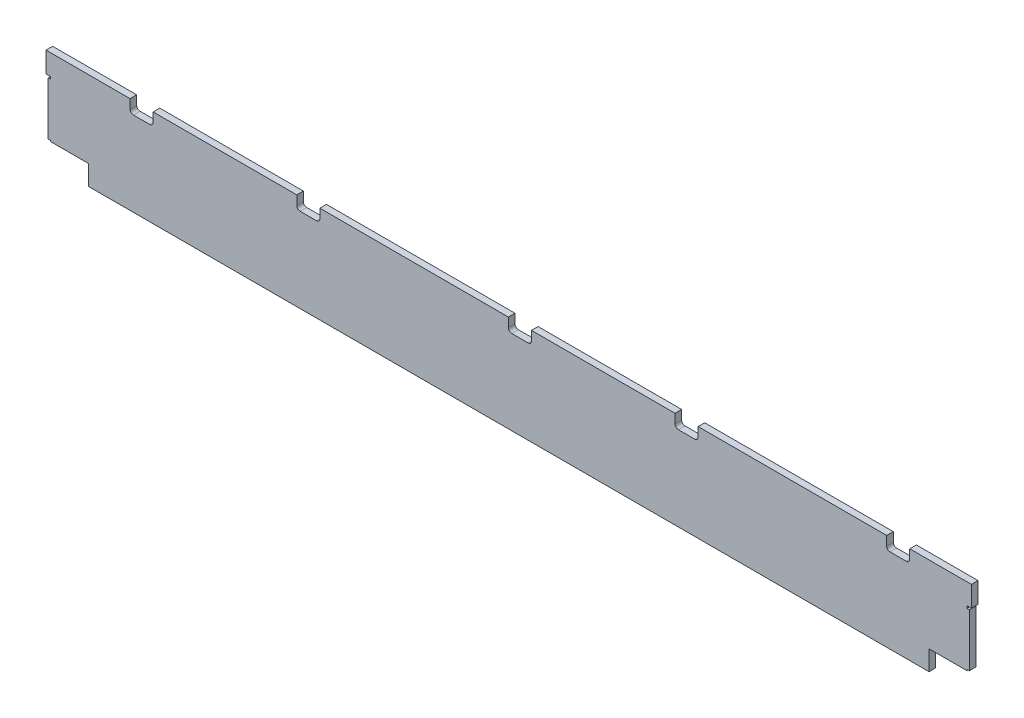
SolidWorks part; units mm, degrees
material "PP Film"
ref_plane "X-Y Datum" through (0, 0, 0) normal (0, 0, 1) x (1, 0, 0)
ref_plane "X-Z Datum" through (0, 0, 0) normal (0, 1, 0) x (1, 0, 0)
ref_plane "Y-Z Datum" through (0, 0, 0) normal (1, 0, 0) x (0, 0, -1)
sketch "Sketch2" plane through (0, 0, 0) normal (0, 0, 1) x (1, 0, 0)
  line L20 (249.4468, -203.714) -> (249.4468, -194.181)
  line L21 (249.4468, -194.181) -> (267.6238, -194.181)
  line L22 (267.6238, -194.181) -> (267.6238, -193.665)
  line L23 (267.6238, -193.665) -> (268.7668, -193.665)
  line L24 (268.7668, -193.665) -> (268.7668, -168.265)
  line L25 (268.7668, -168.265) -> (267.6238, -168.265)
  line L26 (267.6238, -168.265) -> (267.6238, -167.122)
  line L27 (267.6238, -167.122) -> (269.7668, -167.122)
  line L28 (269.7668, -167.122) -> (269.7668, -157.216)
  line L29 (269.7668, -157.216) -> (240.1722, -157.216)
  line L30 (-174.4992, -157.216) -> (-174.4992, -167.122)
  line L31 (-174.4992, -167.122) -> (-172.3562, -167.122)
  line L32 (-172.3562, -167.122) -> (-172.3562, -168.265)
  line L33 (-172.3562, -168.265) -> (-173.4992, -168.265)
  line L34 (-173.4992, -168.265) -> (-173.4992, -193.665)
  line L35 (-173.4992, -193.665) -> (-172.3562, -193.665)
  line L36 (-172.3562, -193.665) -> (-172.3562, -194.181)
  line L37 (-172.3562, -194.181) -> (-154.1792, -194.181)
  line L38 (-154.1792, -194.181) -> (-154.1792, -203.714)
  line L39 (-154.1792, -203.714) -> (249.4468, -203.714)
  line L40 (249.4468, -203.714) -> (249.4468, -194.181)
  line L41 (249.4468, -194.181) -> (267.6238, -194.181)
  line L42 (267.6238, -194.181) -> (267.6238, -193.665)
  line L43 (267.6238, -193.665) -> (268.7668, -193.665)
  line L44 (268.7668, -193.665) -> (268.7668, -168.265)
  line L45 (268.7668, -168.265) -> (267.6238, -168.265)
  line L46 (267.6238, -168.265) -> (267.6238, -167.122)
  line L47 (267.6238, -167.122) -> (269.7668, -167.122)
  line L48 (269.7668, -167.122) -> (269.7668, -157.216)
  line L49 (269.7668, -157.216) -> (240.1722, -157.216)
  line L50 (-174.4992, -157.216) -> (-174.4992, -167.122)
  line L51 (-174.4992, -167.122) -> (-172.3562, -167.122)
  line L52 (-172.3562, -167.122) -> (-172.3562, -168.265)
  line L53 (-172.3562, -168.265) -> (-173.4992, -168.265)
  line L54 (-173.4992, -168.265) -> (-173.4992, -193.665)
  line L55 (-173.4992, -193.665) -> (-172.3562, -193.665)
  line L56 (-172.3562, -193.665) -> (-172.3562, -194.181)
  line L57 (-172.3562, -194.181) -> (-154.1792, -194.181)
  line L58 (-154.1792, -194.181) -> (-154.1792, -203.714)
  line L59 (-154.1792, -203.714) -> (249.4468, -203.714)
  line L120 (-124.6433, -163.248) -> (-132.5323, -163.248)
  line L121 (-124.6433, -163.248) -> (-132.5323, -163.248)
  line L122 (-134.1198, -161.6605) -> (-134.1198, -157.216)
  line L123 (-134.1198, -161.6605) -> (-134.1198, -157.216)
  line L124 (-134.1198, -157.216) -> (-174.4992, -157.216)
  line L125 (-134.1198, -157.216) -> (-174.4992, -157.216)
  line L126 (240.1722, -157.216) -> (240.1722, -161.6605)
  line L127 (240.1722, -157.216) -> (240.1722, -161.6605)
  line L128 (238.5847, -163.248) -> (230.6957, -163.248)
  line L129 (238.5847, -163.248) -> (230.6957, -163.248)
  line L130 (229.1082, -161.6605) -> (229.1082, -157.216)
  line L131 (229.1082, -161.6605) -> (229.1082, -157.216)
  line L132 (229.1082, -157.216) -> (138.5734, -157.216)
  line L133 (229.1082, -157.216) -> (138.5734, -157.216)
  line L134 (138.5734, -157.216) -> (138.5734, -161.6605)
  line L135 (138.5734, -157.216) -> (138.5734, -161.6605)
  line L136 (136.9859, -163.248) -> (129.0969, -163.248)
  line L137 (136.9859, -163.248) -> (129.0969, -163.248)
  line L138 (127.5094, -161.6605) -> (127.5094, -157.216)
  line L139 (127.5094, -161.6605) -> (127.5094, -157.216)
  line L140 (127.5094, -157.216) -> (58.5582, -157.216)
  line L141 (127.5094, -157.216) -> (58.5582, -157.216)
  line L142 (58.5582, -157.216) -> (58.5582, -161.6605)
  line L143 (58.5582, -157.216) -> (58.5582, -161.6605)
  line L144 (56.9707, -163.248) -> (49.0817, -163.248)
  line L145 (56.9707, -163.248) -> (49.0817, -163.248)
  line L146 (47.4942, -161.6605) -> (47.4942, -157.216)
  line L147 (47.4942, -161.6605) -> (47.4942, -157.216)
  line L148 (47.4942, -157.216) -> (-43.0406, -157.216)
  line L149 (47.4942, -157.216) -> (-43.0406, -157.216)
  line L150 (-43.0406, -157.216) -> (-43.0406, -161.6605)
  line L151 (-43.0406, -157.216) -> (-43.0406, -161.6605)
  line L152 (-44.6281, -163.248) -> (-52.5171, -163.248)
  line L153 (-44.6281, -163.248) -> (-52.5171, -163.248)
  line L154 (-54.1046, -161.6605) -> (-54.1046, -157.216)
  line L155 (-54.1046, -161.6605) -> (-54.1046, -157.216)
  line L156 (-54.1046, -157.216) -> (-123.0558, -157.216)
  line L157 (-54.1046, -157.216) -> (-123.0558, -157.216)
  line L158 (-123.0558, -157.216) -> (-123.0558, -161.6605)
  line L159 (-123.0558, -157.216) -> (-123.0558, -161.6605)
  arc A20 (-134.1198, -161.6605) -> (-132.5323, -163.248) centre (-132.5323, -161.6605) ccw
  arc A21 (-134.1198, -161.6605) -> (-132.5323, -163.248) centre (-132.5323, -161.6605) ccw
  arc A22 (238.5847, -163.248) -> (240.1722, -161.6605) centre (238.5847, -161.6605) ccw
  arc A23 (238.5847, -163.248) -> (240.1722, -161.6605) centre (238.5847, -161.6605) ccw
  arc A24 (229.1082, -161.6605) -> (230.6957, -163.248) centre (230.6957, -161.6605) ccw
  arc A25 (229.1082, -161.6605) -> (230.6957, -163.248) centre (230.6957, -161.6605) ccw
  arc A26 (136.9859, -163.248) -> (138.5734, -161.6605) centre (136.9859, -161.6605) ccw
  arc A27 (136.9859, -163.248) -> (138.5734, -161.6605) centre (136.9859, -161.6605) ccw
  arc A28 (127.5094, -161.6605) -> (129.0969, -163.248) centre (129.0969, -161.6605) ccw
  arc A29 (127.5094, -161.6605) -> (129.0969, -163.248) centre (129.0969, -161.6605) ccw
  arc A30 (56.9707, -163.248) -> (58.5582, -161.6605) centre (56.9707, -161.6605) ccw
  arc A31 (56.9707, -163.248) -> (58.5582, -161.6605) centre (56.9707, -161.6605) ccw
  arc A32 (47.4942, -161.6605) -> (49.0817, -163.248) centre (49.0817, -161.6605) ccw
  arc A33 (47.4942, -161.6605) -> (49.0817, -163.248) centre (49.0817, -161.6605) ccw
  arc A34 (-44.6281, -163.248) -> (-43.0406, -161.6605) centre (-44.6281, -161.6605) ccw
  arc A35 (-44.6281, -163.248) -> (-43.0406, -161.6605) centre (-44.6281, -161.6605) ccw
  arc A36 (-54.1046, -161.6605) -> (-52.5171, -163.248) centre (-52.5171, -161.6605) ccw
  arc A37 (-54.1046, -161.6605) -> (-52.5171, -163.248) centre (-52.5171, -161.6605) ccw
  arc A38 (-124.6433, -163.248) -> (-123.0558, -161.6605) centre (-124.6433, -161.6605) ccw
  arc A39 (-124.6433, -163.248) -> (-123.0558, -161.6605) centre (-124.6433, -161.6605) ccw
  dimension "D1" = 0
extrude "Boss-Extrude1" add sketch "Sketch2" along normal blind 3.175 contours L58 L59 L40 L41 L42 L43 L44 L45 L46 L47 L48 L49 L50 L51 L52 L53 L54 L55 L56 L57 region at (47.6161, -180.44, 0)
